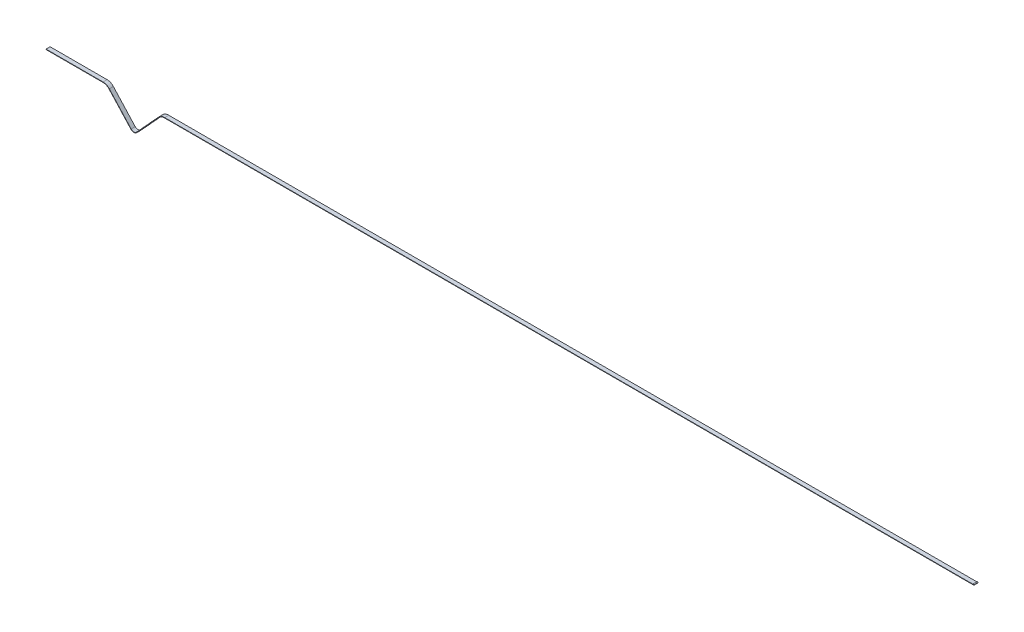
SolidWorks part; units mm, degrees
ref_plane "Front Plane" through (0, 0, 0) normal (0, 0, 1) x (1, 0, 0)
ref_plane "Top Plane" through (0, 0, 0) normal (0, 1, 0) x (1, 0, 0)
ref_plane "Right Plane" through (0, 0, 0) normal (1, 0, 0) x (0, 0, -1)
sketch "Sketch1" plane through (0, 0, 0) normal (1, 0, 0) x (0, 0, -1)
  line L1 (0, 0) -> (6, 0)
  line L2 (0, 0) -> (0, 0.63)
  line L3 (0, 0.63) -> (6, 0.63)
  line L4 (6, 0) -> (6, 0.63)
  dimension "D1" = 0.63
  dimension "D2" = 6
sketch "Sketch2" plane through (0, 0, 0) normal (0, 0, 1) x (1, 0, 0)
  line L0 (0, 0) -> (-1196.1643, 0)
  line L1 (-1204.9833, -3.886) -> (-1237.2251, -39.1468)
  line L2 (-1246.2434, -39.1468) -> (-1278.4853, -3.886)
  line L3 (-1287.3043, 0) -> (-1371.6, 0)
  arc A0 (-1196.1643, 0) -> (-1204.9833, -3.886) centre (-1196.1643, -11.95) ccw
  arc A1 (-1237.2251, -39.1468) -> (-1246.2434, -39.1468) centre (-1241.7343, -35.0237) cw
  arc A2 (-1278.4853, -3.886) -> (-1287.3043, 0) centre (-1287.3043, -11.95) ccw
  circle A3 centre (-1196.1643, -11.95) radius 11.95 construction
  circle A4 centre (-1287.3043, -11.95) radius 11.95 construction
  circle A5 centre (-1241.7343, -35.0237) radius 6.11 construction
  dimension "D1" = 6.11
  dimension "D4" = 1371.6
sweep "Sweep1" add profiles "Sketch1" path "Sketch2"
sketch "Sketch3" plane through (0, 0, 0) normal (0, 0, 1) x (1, 0, 0)
  line L0 (0, 0.63) -> (-1196.1643, 0.63) construction
  line L1 (-1.5, 0.63) -> (-1.5, 0)
  line L2 (0, 0) -> (-1196.1643, 0) construction
  line L3 (-1.5, 0) -> (0, 0)
  line L4 (0, 0) -> (0, 0.63)
  arc A1 (0, 0.63) -> (-1.5, 0.63) centre (-0.75, 0.63) ccw
  dimension "D1" = 0.75
extrude "Boss-Extrude1" add sketch "Sketch3" against normal through all
pattern_curve "CrvPattern1" [suppressed] of bodies 102 driven by "Sketch2" parameters "D1"=2000, "D3"=2, "D2"=1, "D4"=10
